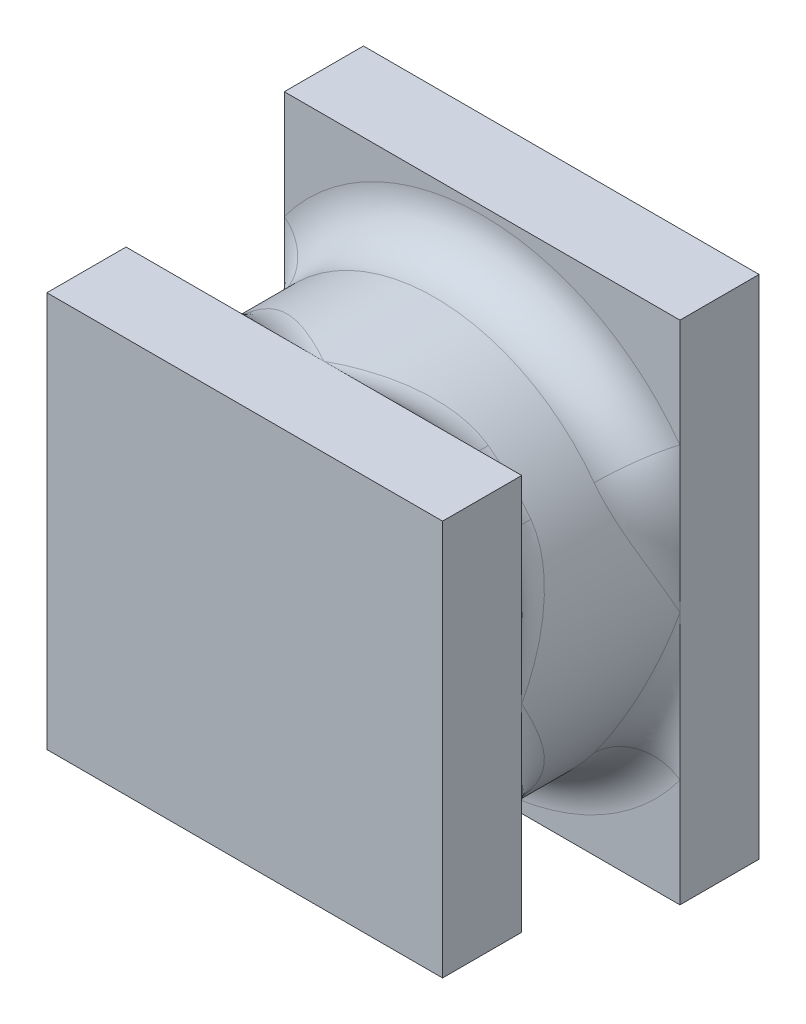
SolidWorks part; units mm, degrees
ref_plane "Спереди" through (0, 0, 0) normal (0, 0, 1) x (1, 0, 0)
ref_plane "Сверху" through (0, 0, 0) normal (0, 1, 0) x (1, 0, 0)
ref_plane "Справа" through (0, 0, 0) normal (1, 0, 0) x (0, 0, -1)
sketch "Эскиз1" plane through (0, 0, 0) normal (0, 0, 1) x (1, 0, 0)
  line L1 (-1.25, 1.6) -> (1.25, 1.6)
  line L2 (-1.25, 1.6) -> (-1.25, -1.6)
  line L3 (-1.25, -1.6) -> (1.25, -1.6)
  line L4 (1.25, 1.6) -> (1.25, -1.6)
  line L5 (-1.25, 1.6) -> (1.25, -1.6) construction
  line L6 (-1.25, -1.6) -> (1.25, 1.6) construction
  point P0 (0, 0)
  dimension "D1" = 3.2
  dimension "D2" = 2.5
extrude "Бобышка-Вытянуть1" add sketch "Эскиз1" along normal blind 0.5
sketch "Эскиз2" plane through (0, 0, 0.5) normal (0, 0, 1) x (1, 0, 0)
  circle A0 centre (0, 0) radius 1.25
  dimension "D1" = 2.5
extrude "Бобышка-Вытянуть2" add sketch "Эскиз2" along normal blind 1
sketch "Эскиз3" plane through (0, 0, 1.5) normal (0, 0, 1) x (1, 0, 0)
  line L1 (-1.25, -1.25) -> (1.25, -1.25)
  line L2 (-1.25, -1.25) -> (-1.25, 1.25)
  line L3 (-1.25, 1.25) -> (1.25, 1.25)
  line L4 (1.25, -1.25) -> (1.25, 1.25)
  line L5 (-1.25, -1.25) -> (1.25, 1.25) construction
  line L6 (-1.25, 1.25) -> (1.25, -1.25) construction
  point P0 (0, 0)
  dimension "D1" = 2.5
extrude "Бобышка-Вытянуть3" add sketch "Эскиз3" along normal blind 0.5
fillet "Скругление1" radius 0.3 2 edges at (0, -1.25, 0.5) (0, 1.25, 0.5)
fillet "Скругление2" radius 0.3 4 edges at (0.8839, 0.8839, 1.5) (-0.8839, 0.8839, 1.5) (0.8839, -0.8839, 1.5) (-0.8839, -0.8839, 1.5)
